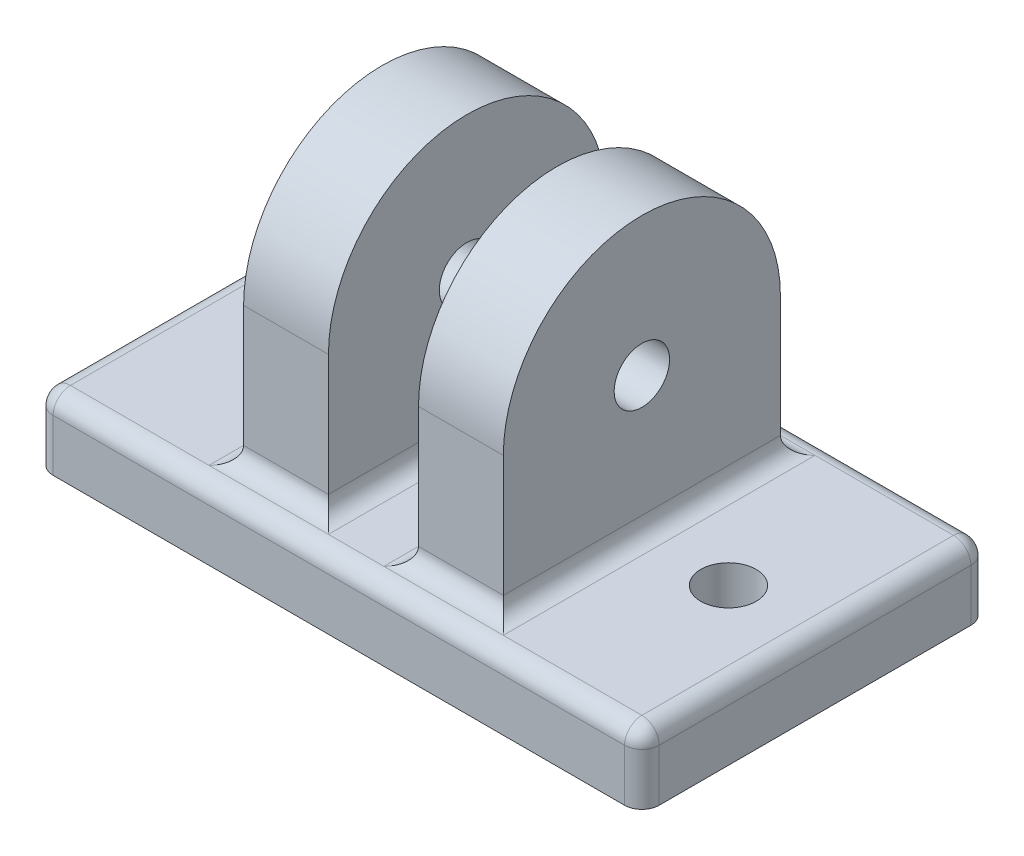
SolidWorks part; units mm, degrees
ref_plane "Front Plane" through (0, 0, 0) normal (1, 0, 0) x (0, 1, 0)
ref_plane "Top Plane" through (0, 0, 0) normal (0, 0, 1) x (0, 1, 0)
ref_plane "Right Plane" through (0, 0, 0) normal (0, 1, 0) x (-1, 0, 0)
sketch "Sketch1" plane through (0, 0, 0) normal (1, 0, 0) x (0, 1, 0)
  line L1 (-10, 10) -> (10, 10)
  line L2 (-10, 10) -> (-10, -10)
  line L3 (-10, -10) -> (10, -10)
  line L4 (10, 10) -> (10, -10)
  line L5 (-10, 10) -> (10, -10) construction
  line L6 (-10, -10) -> (10, 10) construction
  point P0 (0, 0)
  dimension "D1" = 20
  dimension "D2" = 20
extrude "Boss-Extrude1" add sketch "Sketch1" along normal blind 15
ref_plane "Plane1" through (7.5, 0, 0) normal (-1, 0, 0) x (0, 0, 1)
sketch "Sketch2" plane through (7.5, 0, 0) normal (-1, 0, 0) x (0, 0, 1)
  line L1 (-10, -10) -> (-10, 10) construction
  line L2 (-10, 0) -> (-10, 10)
  line L3 (-10, 10) -> (10, 10) construction
  line L5 (10, 10) -> (10, 0)
  line L6 (10, 10) -> (10, -10) construction
  line L8 (-8, 2) -> (-8, -6)
  line L9 (-8, -6) -> (-10, -6)
  line L10 (-10, -6) -> (-10, 0)
  line L11 (-10, 10) -> (10, 10)
  line L12 (0, 0) -> (0, 14.4574) construction
  line L13 (10, -6) -> (10, 0)
  line L14 (8, -6) -> (10, -6)
  line L15 (8, 2) -> (8, -6)
  line L16 (10, 0) -> (10, 10)
  arc A0 (-8, 2) -> (8, 2) centre (0, 2) cw
  point P20 (0, 10)
  dimension "D1" = 8
  dimension "D2" = 2
  dimension "D3" = 8
extrude "Cut-Extrude1" cut sketch "Sketch2" against normal through all both and the other way through all contours L8 A0 L11 L2 L10 L9 | L11 A0 L15 L14 L13 L5 region at (7.5, 3.8658, 8.1631) region at (7.5, 3.8658, -8.1631)
sketch "Sketch3" plane through (7.5, 0, 0) normal (-1, 0, 0) x (0, 0, 1)
  line L0 (-10, -6) -> (10, -6)
  line L1 (-10, -10) -> (-10, -6) construction
  line L2 (10, -6) -> (10, -10) construction
  line L3 (10, -6) -> (10, 10)
  line L4 (10, 10) -> (-10, 10)
  line L5 (-10, 10) -> (-10, -6)
  arc A0 (8, 2) -> (-8, 2) centre (0, 2) ccw construction
  dimension "D1" = 16
extrude "Cut-Extrude2" cut sketch "Sketch3" against normal mid plane 5.2
sketch "Sketch4" plane through (7.5, 0, 0) normal (-1, 0, 0) x (0, 0, 1)
  circle A0 centre (0, 2) radius 1.6
  dimension "D1" = 3.2
extrude "Cut-Extrude3" cut sketch "Sketch4" against normal through all both and the other way through all
sketch "Sketch5" plane through (7.5, 0, 0) normal (-1, 0, 0) x (0, 0, 1)
  line L1 (-10, -10) -> (10, -10)
  line L2 (-10, -10) -> (-10, -6)
  line L3 (-10, -6) -> (10, -6)
  line L4 (10, -10) -> (10, -6)
extrude "Boss-Extrude2" add sketch "Sketch5" along normal mid plane 35
sketch "Sketch6" plane through (0, -6, 0) normal (0, 1, 0) x (1, 0, 0)
  line L4 (25, -10) -> (25, 10) construction
  line L6 (7.5, 8.8) -> (7.5, -8.8) construction
  circle A0 centre (20, 0) radius 1.6
  circle A1 centre (-5, 0) radius 1.6
  point P2 (0, 0)
  dimension "D1" = 3.2
  dimension "D2" = 5
extrude "Cut-Extrude4" cut sketch "Sketch6" against normal through all both and the other way through all
fillet "Fillet4" radius 1 16 edges at (12.55, -6, -8) (10.1, -6, 0) (12.55, -6, 8) (15, -6, 0) (0, -6, 0) (2.45, -6, 8) (4.9, -6, 0) (2.45, -6, -8) (-10, -6, 0) (7.5, -6, -10) (25, -6, 0) (7.5, -6, 10) (-10, -8, -10) (-10, -8, 10) (25, -8, 10) (25, -8, -10)
